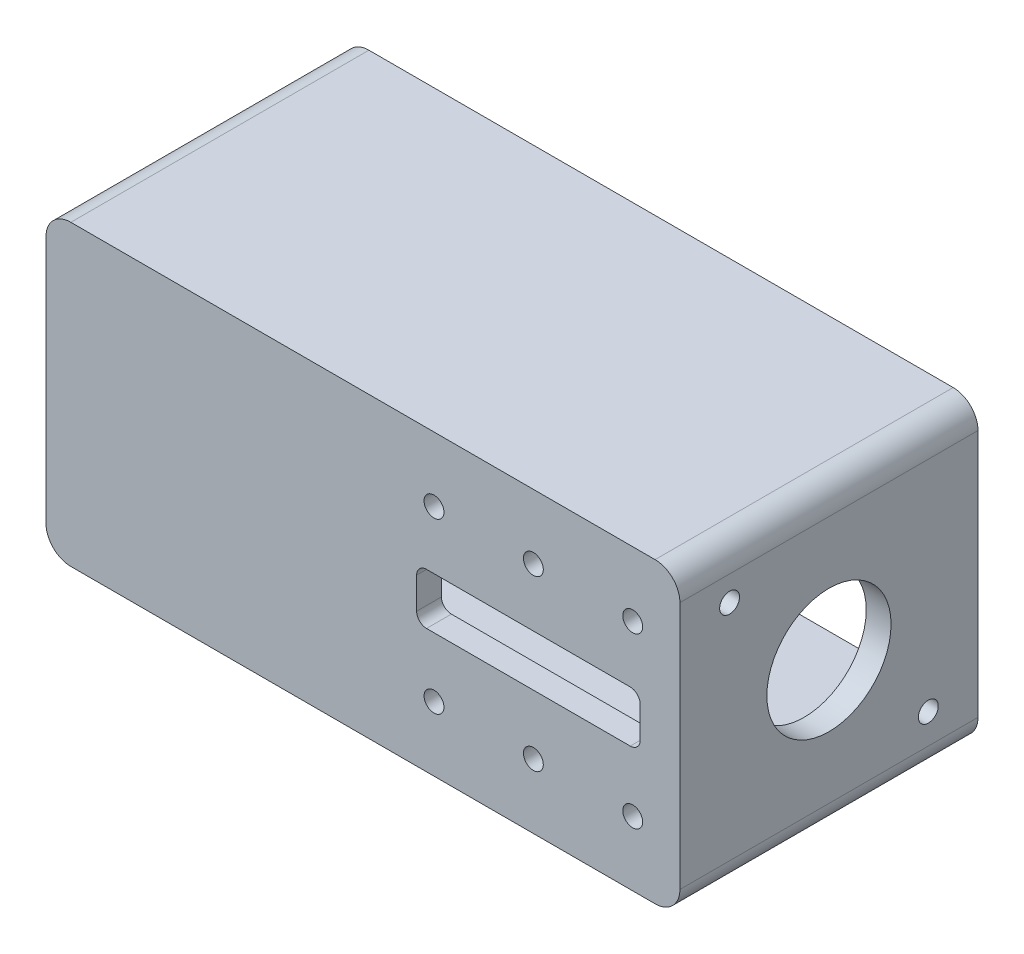
SolidWorks part; units mm, degrees
material "AISI 316 Annealed Stainless Steel Bar (SS)"
ref_plane "Front Plane" through (0, 0, 0) normal (0, 0, 1) x (1, 0, 0)
ref_plane "Top Plane" through (0, 0, 0) normal (0, 1, 0) x (1, 0, 0)
ref_plane "Right Plane" through (0, 0, 0) normal (1, 0, 0) x (0, 0, -1)
sketch "Sketch1" plane through (0, 0, 0) normal (0, 0, 1) x (1, 0, 0)
  line L1 (-58.8, -30.15) -> (58.8, -30.15)
  line L2 (-63.8, -25.15) -> (-63.8, 24.85)
  line L3 (-58.8, 29.85) -> (58.8, 29.85)
  line L4 (63.8, -25.15) -> (63.8, 24.85)
  line L7 (53.8, 5.15) -> (12.8, 5.15)
  line L8 (55.8, 3.15) -> (55.8, -3.15)
  line L9 (53.8, -5.15) -> (12.8, -5.15)
  line L10 (10.8, 3.15) -> (10.8, -3.15)
  line L11 (59.948, 27.7368) -> (63.8, 29.85) construction
  arc A4 (53.8, -5.15) -> (55.8, -3.15) centre (53.8, -3.15) ccw
  arc A5 (12.8, 5.15) -> (10.8, 3.15) centre (12.8, 3.15) ccw
  arc A6 (12.8, -5.15) -> (10.8, -3.15) centre (12.8, -3.15) cw
  arc A7 (53.8, 5.15) -> (55.8, 3.15) centre (53.8, 3.15) cw
  arc A8 (-58.8, 29.85) -> (-63.8, 24.85) centre (-58.8, 24.85) ccw
  arc A9 (-63.8, -25.15) -> (-58.8, -30.15) centre (-58.8, -25.15) ccw
  arc A10 (63.8, 24.85) -> (58.8, 29.85) centre (58.8, 24.85) ccw
  arc A11 (58.8, -30.15) -> (63.8, -25.15) centre (58.8, -25.15) ccw
  point P0 (0, 0)
  point P2 (10.8, 0)
  dimension "D4" = 2
  dimension "D9" = 5
  dimension "D2" = 5
  dimension "D10" = 5
  dimension "D11" = 5
  dimension "D3" = 60
  dimension "D5" = 45
  dimension "D6" = 10.3
  dimension "D7" = 8
  dimension "D8" = 25
extrude "Boss-Extrude1" add sketch "Sketch1" along normal blind 60 contours L3 A10 L4 A11 L1 A9 L2 A8 | L8 A4 L9 A6 L10 A5 L7 A7
sketch "Sketch2" plane through (0, 0, 0) normal (0, 0, -1) x (-1, 0, 0)
  line L4 (0, 0) -> (23.7682, 0) construction
  line L17 (-58.8, 24.85) -> (-58.8, -25.15)
  line L18 (-58.8, -25.15) -> (58.8, -25.15)
  line L19 (58.8, -25.15) -> (58.8, 24.85)
  line L20 (58.8, 24.85) -> (-58.8, 24.85)
  line L21 (-58.8, 24.85) -> (-58.8, -25.15)
  line L22 (-58.8, -25.15) -> (58.8, -25.15)
  line L23 (58.8, -25.15) -> (58.8, 24.85)
  line L24 (58.8, 24.85) -> (-58.8, 24.85)
  dimension "D1" = 5
  dimension "D6" = 23.7682
sketch "Sketch3" plane through (0, 0, 60) normal (0, 0, 1) x (1, 0, 0)
  line L2 (63.8, -25.15) -> (63.8, 24.85) construction
  line L3 (-58.8, 29.85) -> (58.8, 29.85) construction
  circle A0 centre (14.3, 16.85) radius 2
  circle A1 centre (34.3, 16.85) radius 2
  circle A2 centre (54.3, 16.85) radius 2
  circle A3 centre (34.3, -17.15) radius 2
  circle A4 centre (54.3, -17.15) radius 2
  circle A5 centre (14.3, -17.15) radius 2
  dimension "D2" = 4
  dimension "D1" = 9.5
  dimension "D3" = 13
  dimension "D6" = 20
  dimension "D7" = 34
  dimension "D8" = 9.5
  dimension "D4" = 3
  dimension "D5" = 2
extrude "Cut-Extrude2" cut sketch "Sketch3" against normal blind 35
sketch "Sketch4" plane through (0, 0, 60) normal (0, 0, 1) x (1, 0, 0)
  line L0 (53.8, -5.15) -> (12.8, -5.15) construction
  line L2 (63.8, -25.15) -> (63.8, 24.85) construction
  circle A0 centre (61.3, -0.05) radius 0.75
  dimension "D1" = 1.5
  dimension "D2" = 5.1
  dimension "D3" = 2.5
extrude "Cut-Extrude4" cut sketch "Sketch2" against normal blind 55
sketch "Sketch12" plane through (0, 0, 55) normal (0, 0, -1) x (-1, 0, 0)
  line L0 (58.8, -25.15) -> (58.8, 24.85) construction
  line L1 (38.8039, 24.85) -> (53.8, 24.85)
  line L2 (38.8039, 24.85) -> (38.8039, -25.15)
  line L3 (38.8039, -25.15) -> (58.8, -25.15)
  line L4 (58.8, 19.85) -> (58.8, -25.15)
  line L5 (58.8, 24.85) -> (-58.8, 24.85) construction
  line L6 (53.8, 24.85) -> (58.8, 24.85)
  line L7 (58.8, 19.85) -> (58.8, 24.85)
  dimension "D1" = 50
  dimension "D2" = 5
  dimension "D3" = 5
extrude "Boss-Extrude2" add sketch "Sketch12" along normal blind 50
sketch "Sketch8" plane through (-63.8, 0, 0) normal (-1, 0, 0) x (0, 0, 1)
  line L4 (60, -25.15) -> (60, 24.85) construction
  line L5 (60, 29.85) -> (0, 29.85) construction
  circle A2 centre (30, -0.15) radius 12.7
  dimension "D1" = 30
  dimension "D3" = 25.4
  dimension "D2" = 30
extrude "Cut-Extrude5" cut sketch "Sketch8" against normal blind 35
sketch "Sketch13" plane through (-63.8, 0, 0) normal (-1, 0, 0) x (0, 0, 1)
  circle A0 centre (10, -19.15) radius 2
  circle A1 centre (50, 19.85) radius 2
  circle A2 centre (30, -0.15) radius 12.7 construction
  dimension "D1" = 20
  dimension "D2" = 20
  dimension "D3" = 19
  dimension "D5" = 4
  dimension "D6" = 4
  dimension "D4" = 20
extrude "Cut-Extrude6" cut sketch "Sketch13" against normal through all
sketch "Sketch14" plane through (0, 0, 5) normal (0, 0, -1) x (-1, 0, 0)
  line L0 (38.8039, 24.85) -> (38.8039, -25.15) construction
  line L2 (58.8, -30.15) -> (-58.8, -30.15) construction
  circle A0 centre (52.6439, -0.15) radius 1.5
  circle A1 centre (42.0439, 15.05) radius 1.5
  circle A2 centre (42.0439, -15.35) radius 1.5
  dimension "D1" = 3
  dimension "D2" = 3
  dimension "D6" = 15.2
  dimension "D7" = 15.2
  dimension "D3" = 13.84
  dimension "D4" = 10.6
  dimension "D5" = 30
extrude "Cut-Extrude7" cut sketch "Sketch14" against normal blind 10
ref_plane "Plane1" through (56.1961, 0, 0) normal (1, 0, 0) x (0, 0, -1)
sketch "Sketch16" plane through (56.1961, 0, 0) normal (1, 0, 0) x (0, 0, -1)
  line L0 (-60, -25.15) -> (-60, 24.85) construction
  line L1 (-60, -30.15) -> (0, -30.15) construction
  circle A0 centre (-30, -0.15) radius 12.5
  dimension "D1" = 25
  dimension "D2" = 30
  dimension "D3" = 30
extrude "Cut-Extrude8" cut sketch "Sketch16" along normal blind 10
sketch "Sketch17" plane through (0, 0, 0) normal (0, 0, -1) x (-1, 0, 0)
  line L0 (58.8, 29.85) -> (-58.8, 29.85) construction
  line L1 (-63.8, -25.15) -> (-63.8, 24.85) construction
  circle A0 centre (-53.8, 27.35) radius 1.5
  dimension "D1" = 3
  dimension "D2" = 2.5
  dimension "D3" = 10
extrude "Cut-Extrude9" cut sketch "Sketch17" against normal blind 20
sketch "Sketch18" plane through (0, 0, 0) normal (0, 0, -1) x (-1, 0, 0)
  line L0 (-63.8, -25.15) -> (-63.8, 24.85) construction
  line L1 (58.8, 29.85) -> (-58.8, 29.85) construction
  line L2 (58.8, -30.15) -> (-58.8, -30.15) construction
  circle A0 centre (-61.3, 9.85) radius 1.5
  circle A1 centre (-61.3, -10.15) radius 1.5
  dimension "D2" = 3
  dimension "D4" = 2.5
  dimension "D6" = 3
  dimension "D1" = 2.5
  dimension "D3" = 20
  dimension "D5" = 20
extrude "Cut-Extrude10" cut sketch "Sketch18" against normal blind 20
pattern_linear "LPattern1" count 4 spacing 35 along (-1, 0, 0) count 2 spacing 55 along (0, -1, 0) of "Cut-Extrude9"
mirror "Mirror1" about plane through (0, 0, 0) normal (1, 0, 0) of "Cut-Extrude10"
sketch "Sketch19" plane through (0, 0, 0) normal (0, 0, -1) x (-1, 0, 0)
  line L4 (58.8, 29.85) -> (-58.8, 29.85)
  line L5 (-63.8, 24.85) -> (-63.8, -25.15)
  line L6 (-58.8, -30.15) -> (58.8, -30.15)
  line L7 (63.8, -25.15) -> (63.8, 24.85)
  line L8 (58.8, 29.85) -> (-58.8, 29.85)
  line L9 (-63.8, 24.85) -> (-63.8, -25.15)
  line L10 (-58.8, -30.15) -> (58.8, -30.15)
  line L11 (63.8, -25.15) -> (63.8, 24.85)
  circle A0 centre (-61.3, -10.15) radius 1.5 construction
  circle A1 centre (-61.3, 9.85) radius 1.5 construction
  circle A2 centre (-53.8, 27.35) radius 1.5 construction
  circle A3 centre (-61.3, -10.15) radius 1.5
  arc A4 (63.8, 24.85) -> (58.8, 29.85) centre (58.8, 24.85) ccw
  arc A5 (-58.8, 29.85) -> (-63.8, 24.85) centre (-58.8, 24.85) ccw
  arc A6 (-63.8, -25.15) -> (-58.8, -30.15) centre (-58.8, -25.15) ccw
  arc A7 (58.8, -30.15) -> (63.8, -25.15) centre (58.8, -25.15) ccw
  arc A8 (63.8, 24.85) -> (58.8, 29.85) centre (58.8, 24.85) ccw
  arc A9 (-58.8, 29.85) -> (-63.8, 24.85) centre (-58.8, 24.85) ccw
  arc A10 (-63.8, -25.15) -> (-58.8, -30.15) centre (-58.8, -25.15) ccw
  arc A11 (58.8, -30.15) -> (63.8, -25.15) centre (58.8, -25.15) ccw
  circle A12 centre (-61.3, 9.85) radius 1.5
  circle A13 centre (-53.8, 27.35) radius 1.5
  circle A14 centre (-18.8, 27.35) radius 1.5 construction
  dimension "D5" = 20
  dimension "D7" = 20
  dimension "D8" = 35
  dimension "D2" = 127.6
  dimension "D3" = 60
  dimension "D4" = 2.5
  dimension "D6" = 10
  dimension "D1" = 0
sketch "Sketch20" plane through (0, 0, 0) normal (0, 0, -1) x (-1, 0, 0)
  line L4 (58.8, 29.85) -> (-58.8, 29.85)
  line L5 (-63.8, 24.85) -> (-63.8, -25.15)
  line L6 (-58.8, -30.15) -> (58.8, -30.15)
  line L7 (63.8, -25.15) -> (63.8, 24.85)
  line L8 (58.8, 29.85) -> (-58.8, 29.85)
  line L9 (-63.8, 24.85) -> (-63.8, -25.15)
  line L10 (-58.8, -30.15) -> (58.8, -30.15)
  line L11 (63.8, -25.15) -> (63.8, 24.85)
  arc A4 (63.8, 24.85) -> (58.8, 29.85) centre (58.8, 24.85) ccw
  arc A5 (-58.8, 29.85) -> (-63.8, 24.85) centre (-58.8, 24.85) ccw
  arc A6 (-63.8, -25.15) -> (-58.8, -30.15) centre (-58.8, -25.15) ccw
  arc A7 (58.8, -30.15) -> (63.8, -25.15) centre (58.8, -25.15) ccw
  arc A8 (63.8, 24.85) -> (58.8, 29.85) centre (58.8, 24.85) ccw
  arc A9 (-58.8, 29.85) -> (-63.8, 24.85) centre (-58.8, 24.85) ccw
  arc A10 (-63.8, -25.15) -> (-58.8, -30.15) centre (-58.8, -25.15) ccw
  arc A11 (58.8, -30.15) -> (63.8, -25.15) centre (58.8, -25.15) ccw
  dimension "D2" = 127.6
  dimension "D3" = 60
  dimension "D1" = 0
fillet "Fillet1" radius 10 4 edges at (-38.8039, -25.15, 30) (58.8, -25.15, 27.5) (58.8, 24.85, 27.5) (-38.8039, 24.85, 30)
